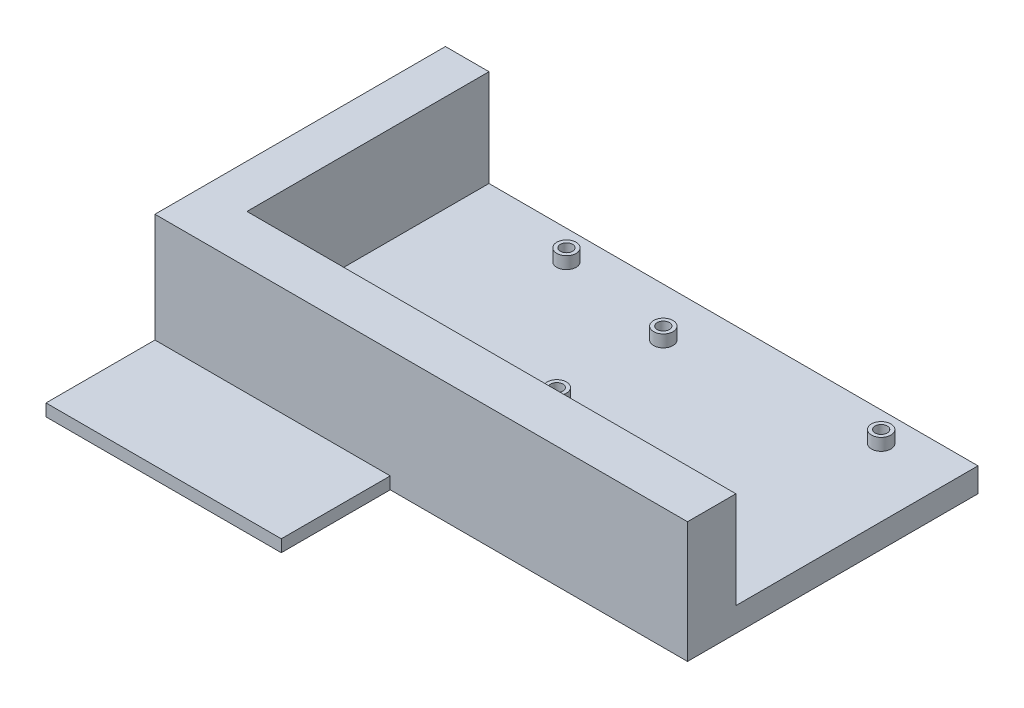
SolidWorks part; units mm, degrees
ref_plane "Front Plane" through (0, 0, 0) normal (0, 0, 1) x (1, 0, 0)
ref_plane "Top Plane" through (0, 0, 0) normal (0, 1, 0) x (1, 0, 0)
ref_plane "Right Plane" through (0, 0, 0) normal (1, 0, 0) x (0, 0, -1)
sketch "Sketch1" plane through (0, 0, 0) normal (0, 1, 0) x (1, 0, 0)
  line L0 (-69.85, -38.1) -> (69.85, -38.1)
  line L1 (-69.85, -38.1) -> (-69.85, 38.1)
  line L2 (69.85, -38.1) -> (69.85, 38.1)
  line L3 (-69.85, 38.1) -> (69.85, 38.1)
  line L4 (-69.85, -38.1) -> (69.85, 38.1) construction
  line L5 (69.85, -38.1) -> (-69.85, 38.1) construction
  line L10 (-58.42, -26.67) -> (58.42, 26.67) construction
  line L11 (58.42, -26.67) -> (-58.42, 26.67) construction
  point P1 (0, 0)
  point P2 (0, 0)
  dimension "D1" = 76.2
  dimension "D2" = 139.7
extrude "Boss-Extrude1" add sketch "Sketch1" along normal blind 31.75
sketch "Sketch2" plane through (0, 31.75, 0) normal (0, 1, 0) x (1, 0, 0)
  line L0 (-58.42, -25.4) -> (69.85, -25.4)
  line L1 (-58.42, -25.4) -> (-58.42, 38.1459)
  line L2 (69.85, -25.4) -> (69.85, 38.1459)
  line L3 (-58.42, 38.1459) -> (69.85, 38.1459)
  line L4 (69.85, -38.1) -> (69.85, 38.1) construction
  line L5 (-69.85, 38.1) -> (-69.85, -38.1) construction
  line L9 (-69.85, -38.1) -> (69.85, -38.1) construction
  dimension "D1" = 11.43
  dimension "D2" = 12.7
extrude "Cut-Extrude1" cut sketch "Sketch2" against normal blind 25.4
sketch "Sketch3" plane through (0, 6.35, 0) normal (0, 1, 0) x (1, 0, 0)
  line L0 (-58.42, -25.4) -> (-48.26, -25.4)
  line L1 (-58.42, -25.4) -> (-58.42, -15.24)
  line L2 (-48.26, -25.4) -> (-48.26, -15.24)
  line L3 (-58.42, -15.24) -> (-48.26, -15.24)
  line L4 (-58.42, -25.4) -> (69.85, -25.4) construction
  dimension "D1" = 10.16
  dimension "D2" = 10.16
extrude "Boss-Extrude3" add sketch "Sketch3" along normal blind 12.7
sketch "Sketch4" plane through (0, 19.05, 0) normal (0, 1, 0) x (1, 0, 0)
  line L0 (-48.26, -25.4) -> (-48.26, -15.24) construction
  line L1 (-48.26, -15.24) -> (-58.42, -15.24) construction
  circle A0 centre (-53.34, -20.32) radius 2.032
  point P4 (-48.26, -20.32)
  dimension "D1" = 4.064
  dimension "D2" = 5.08
  dimension "D3" = 5.08
extrude "Cut-Extrude2" cut sketch "Sketch4" against normal through all
sketch "Sketch5" plane through (0, 19.05, 0) normal (0, 1, 0) x (1, 0, 0)
  circle A0 centre (-53.34, -20.32) radius 3.937
extrude "Cut-Extrude3" cut sketch "Sketch5" against normal blind 2.286
sketch "Sketch6" plane through (0, 0, 38.1) normal (0, 0, 1) x (1, 0, 0)
  line L1 (-69.85, 0) -> (-8.128, 0)
  line L2 (-69.85, 0) -> (-69.85, 3.175)
  line L3 (-69.85, 3.175) -> (-8.128, 3.175)
  line L4 (-8.128, 0) -> (-8.128, 3.175)
  dimension "D1" = 61.722
  dimension "D2" = 3.175
extrude "Boss-Extrude4" add sketch "Sketch6" along normal blind 28.575
sketch "Sketch7" plane through (0, 6.35, 0) normal (0, 1, 0) x (1, 0, 0)
  line L1 (-58.42, 38.1) -> (69.85, 38.1) construction
  circle A0 centre (-30.48, 30.48) radius 1.6002
  circle A1 centre (-24.13, -17.78) radius 1.6002
  circle A2 centre (0, -2.54) radius 1.6002
  circle A3 centre (0, 25.4) radius 1.6002
  circle A4 centre (52.07, 30.48) radius 1.6002
  circle A5 centre (50.8, -17.78) radius 1.6002
  circle A6 centre (-30.48, 30.48) radius 2.54
  circle A7 centre (-24.13, -17.78) radius 2.54
  circle A8 centre (0, 25.4) radius 2.54
  circle A9 centre (0, -2.54) radius 2.54
  circle A10 centre (50.8, -17.78) radius 2.54
  circle A11 centre (52.07, 30.48) radius 2.54
  point P15 (0, 0)
  point P20 (0, 25.4)
  dimension "D1" = 3.2004
  dimension "D10" = 5.08
  dimension "D2" = 6.35
  dimension "D3" = 48.26
  dimension "D4" = 30.48
  dimension "D5" = 5.08
  dimension "D6" = 27.94
  dimension "D7" = 74.93
  dimension "D8" = 82.55
  dimension "D9" = 7.62
extrude "Boss-Extrude5" add sketch "Sketch7" along normal blind 3.175
